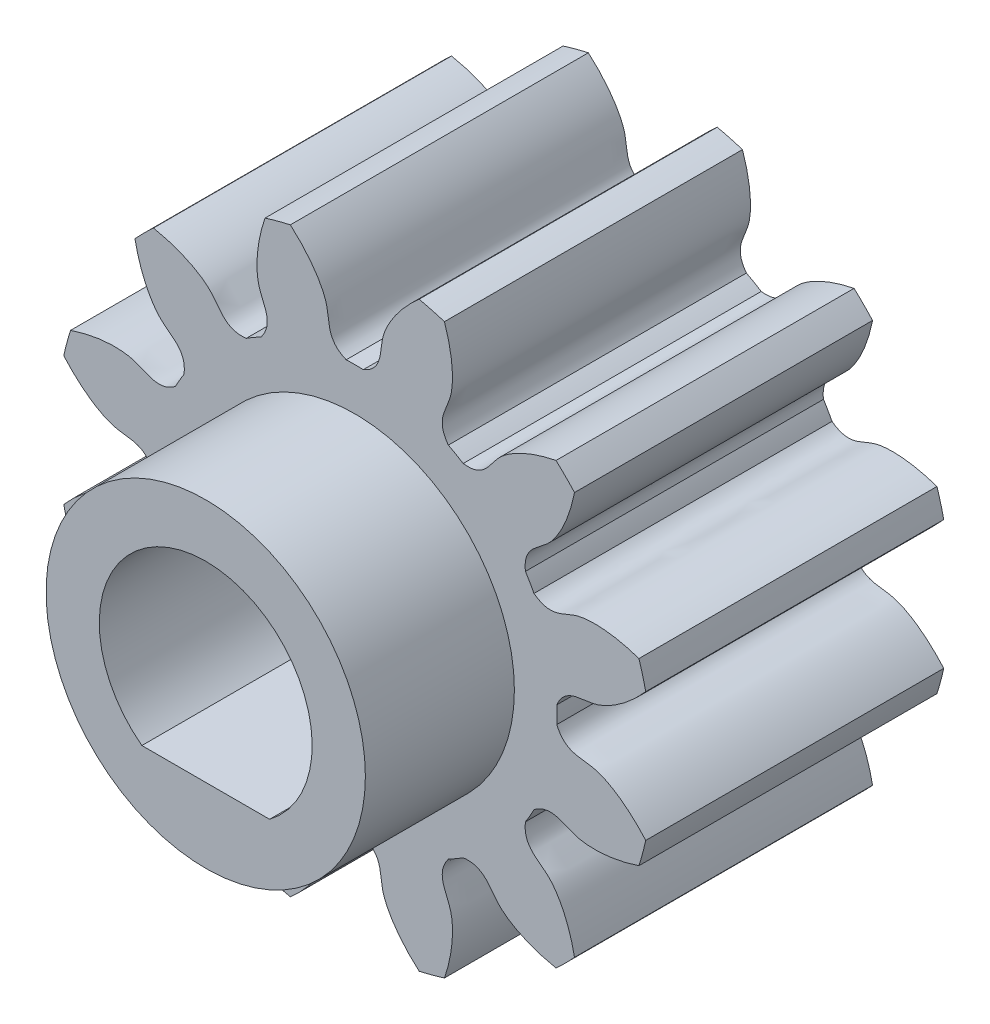
SolidWorks part; units mm, degrees
ref_plane "前视基准面" through (0, 0, 0) normal (0, 0, 1) x (1, 0, 0)
ref_plane "上视基准面" through (0, 0, 0) normal (0, 1, 0) x (1, 0, 0)
ref_plane "右视基准面" through (0, 0, 0) normal (1, 0, 0) x (0, 0, -1)
sketch "草图1" plane through (0, 0, 0) normal (0, 0, 1) x (1, 0, 0)
  circle A0 centre (0, 0) radius 14
extrude "凸台-拉伸1" add sketch "草图1" along normal blind 14
ref_axis "基准轴1" through (0, 0, 14) along (0, 0, -1)
sketch "草图2" plane through (0, 0, 0) normal (0, 0, 1) x (1, 0, 0)
  line L0 (0, 0) -> (0, 14) construction
  circle A0 centre (0, 0) radius 14 construction
  arc A1 (0.4017, 9.4915) -> (-0.4017, 9.4915) centre (0, 0) ccw
  arc A2 (6.9952, 15.7899) -> (-6.9952, 15.7899) centre (0, 0) ccw
  spline S0 degree 3 poles (0.4017, 9.4915) (1.3616, 9.8986) (1.1487, 10.6896) (1.3523, 11.379) (1.3652, 11.4198) (1.3805, 11.4647) (1.3981, 11.5135) (1.4183, 11.5661) (1.4413, 11.6225) (1.4671, 11.6826) (1.4961, 11.7462) (1.5282, 11.8133) (1.5637, 11.8838) (1.6028, 11.9576) (1.6455, 12.0345) (1.6919, 12.1144) (1.7423, 12.1973) (1.7968, 12.2829) (1.8555, 12.3712) (1.9185, 12.462) (1.9859, 12.5552) (2.0579, 12.6506) (2.1346, 12.7481) (2.2161, 12.8475) (2.3025, 12.9487) (2.3939, 13.0516) (2.4904, 13.1559) (2.5921, 13.2615) (2.6991, 13.3682) (2.8114, 13.4759) (2.9292, 13.5844) (3.0525, 13.6935) (3.1814, 13.803) (3.316, 13.9128) (3.4563, 14.0226) (3.6023, 14.1323) (3.7542, 14.2418) (3.912, 14.3507) (4.0756, 14.4589) (4.2452, 14.5663) (4.4208, 14.6726) (4.6024, 14.7776) (4.79, 14.8811) (4.9836, 14.983) (5.1832, 15.083) (5.3889, 15.1809) (5.6006, 15.2765) (5.8183, 15.3697) (6.042, 15.4602) (6.2717, 15.5478) (6.5888, 15.6615) (6.8312, 15.7402) (6.9952, 15.7899) knots 0 0 0 0 0.218015 0.222044 0.226546 0.231522 0.236972 0.242897 0.249295 0.256167 0.263513 0.271332 0.279626 0.288394 0.297636 0.307351 0.317541 0.328204 0.339341 0.350953 0.363038 0.375597 0.38863 0.402137 0.416118 0.430573 0.445502 0.460904 0.476781 0.493132 0.509956 0.527255 0.545027 0.563273 0.581994 0.601188 0.620856 0.640998 0.661614 0.682704 0.704268 0.726305 0.748817 0.771803 0.795262 0.819196 0.843603 0.868484 0.89384 0.919669 0.945972 1 1 1 1
  spline S1 degree 3 poles (-0.4017, 9.4915) (-1.3616, 9.8986) (-1.1487, 10.6896) (-1.3523, 11.379) (-1.3652, 11.4198) (-1.3805, 11.4647) (-1.3981, 11.5135) (-1.4183, 11.5661) (-1.4413, 11.6225) (-1.4671, 11.6826) (-1.4961, 11.7462) (-1.5282, 11.8133) (-1.5637, 11.8838) (-1.6028, 11.9576) (-1.6455, 12.0345) (-1.6919, 12.1144) (-1.7423, 12.1973) (-1.7968, 12.2829) (-1.8555, 12.3712) (-1.9185, 12.462) (-1.9859, 12.5552) (-2.0579, 12.6506) (-2.1346, 12.7481) (-2.2161, 12.8475) (-2.3025, 12.9487) (-2.3939, 13.0516) (-2.4904, 13.1559) (-2.5921, 13.2615) (-2.6991, 13.3682) (-2.8114, 13.4759) (-2.9292, 13.5844) (-3.0525, 13.6935) (-3.1814, 13.803) (-3.316, 13.9128) (-3.4563, 14.0226) (-3.6023, 14.1323) (-3.7542, 14.2418) (-3.912, 14.3507) (-4.0756, 14.4589) (-4.2452, 14.5663) (-4.4208, 14.6726) (-4.6024, 14.7776) (-4.79, 14.8811) (-4.9836, 14.983) (-5.1832, 15.083) (-5.3889, 15.1809) (-5.6006, 15.2765) (-5.8183, 15.3697) (-6.042, 15.4602) (-6.2717, 15.5478) (-6.5888, 15.6615) (-6.8312, 15.7402) (-6.9952, 15.7899) knots 0 0 0 0 0.218015 0.222044 0.226546 0.231522 0.236972 0.242897 0.249295 0.256167 0.263513 0.271332 0.279626 0.288394 0.297636 0.307351 0.317541 0.328204 0.339341 0.350953 0.363038 0.375597 0.38863 0.402137 0.416118 0.430573 0.445502 0.460904 0.476781 0.493132 0.509956 0.527255 0.545027 0.563273 0.581994 0.601188 0.620856 0.640998 0.661614 0.682704 0.704268 0.726305 0.748817 0.771803 0.795262 0.819196 0.843603 0.868484 0.89384 0.919669 0.945972 1 1 1 1
extrude "切除-拉伸1" cut sketch "草图2" along normal through all
pattern_circular "阵列(圆周)1" count 12 every 30 about axis through (0, 0, 14) along (0, 0, -1) of "切除-拉伸1"
sketch "草图3" plane through (0, 0, 0) normal (0, 0, 1) x (1, 0, 0)
  circle A0 centre (0, 0) radius 12 construction
  dimension "Dn" = 24
sketch "草图4" plane through (0, 0, 14) normal (0, 0, 1) x (1, 0, 0)
  circle A0 centre (0, 0) radius 7.5
  dimension "D1" = 15
extrude "凸台-拉伸2" add sketch "草图4" along normal blind 7
sketch "草图5" plane through (0, 0, 21) normal (0, 0, 1) x (1, 0, 0)
  line L0 (3, -4) -> (-3, -4)
  arc A0 (3, -4) -> (-3, -4) centre (0, 0) ccw
  dimension "D1" = 10
  dimension "D2" = 4
extrude "切除-拉伸2" cut sketch "草图5" against normal blind 28
